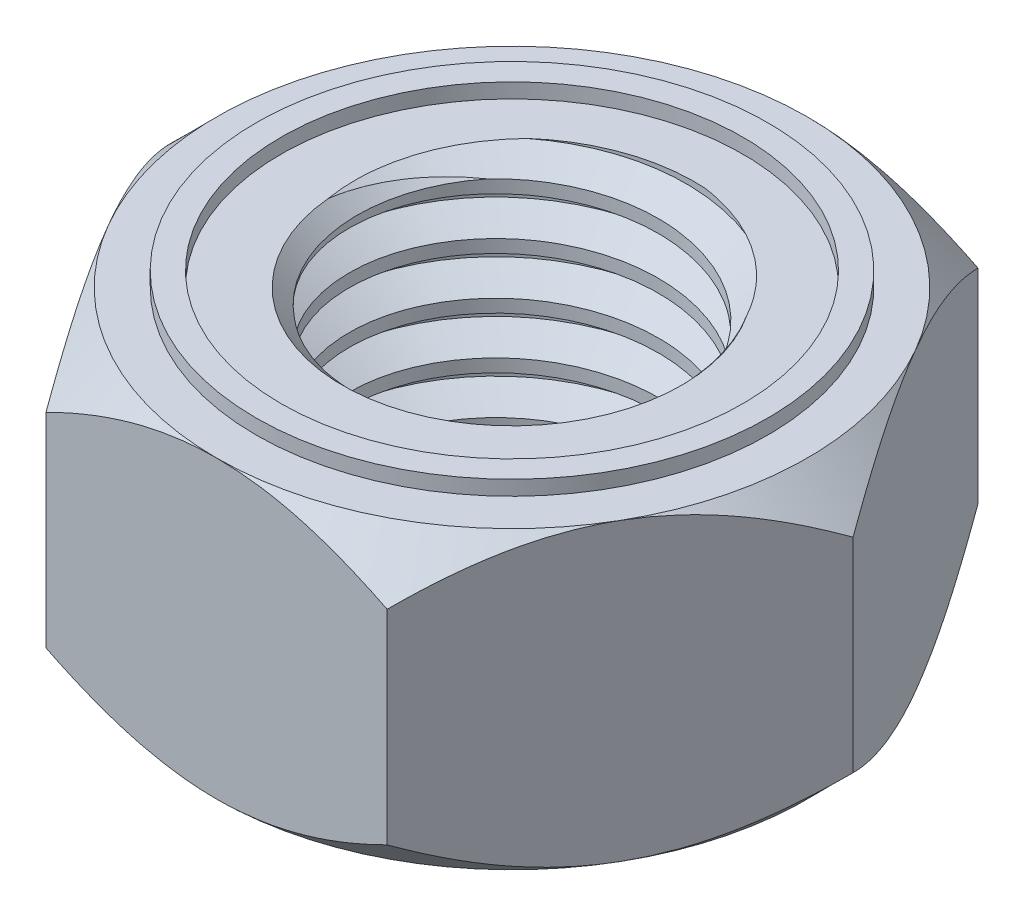
SolidWorks part; units mm, degrees
ref_plane "Front Plane" through (0, 0, 0) normal (0, 0, 1) x (1, 0, 0)
ref_plane "Top Plane" through (0, 0, 0) normal (0, 1, 0) x (1, 0, 0)
ref_plane "Right Plane" through (0, 0, 0) normal (1, 0, 0) x (0, 0, -1)
sketch "Sketch1" plane through (0, 0, 0) normal (0, 1, 0) x (1, 0, 0)
  line L1 (11.547, 0) -> (5.7735, 10)
  line L2 (5.7735, 10) -> (-5.7735, 10)
  line L3 (-5.7735, 10) -> (-11.547, 0)
  line L4 (-11.547, 0) -> (-5.7735, -10)
  line L5 (-5.7735, -10) -> (5.7735, -10)
  line L6 (5.7735, -10) -> (11.547, 0)
  circle A0 centre (0, 0) radius 10 construction
  dimension "D1" = 20
extrude "Boss-Extrude4" add sketch "Sketch1" along normal mid plane 10
sketch "Sketch4" plane through (0, 5, 0) normal (0, 1, 0) x (1, 0, 0)
  line L3 (-5.7735, -10) -> (5.7735, -10) construction
  circle A0 centre (0, 0) radius 10
extrude "Cut-Extrude2" cut sketch "Sketch4" against normal blind 10 draft 45 flip side to cut
mirror "Mirror2" about plane through (0, 0, 0) normal (0, 1, 0) of "Cut-Extrude2"
sketch "Sketch5" plane through (0, 5, 0) normal (0, 1, 0) x (1, 0, 0)
  circle A0 centre (0, 0) radius 5.24
  dimension "D1" = 10.48
extrude "Cut-Extrude3" cut sketch "Sketch5" against normal blind 10
chamfer "Chamfer1" distance 0.5 angle 45 2 edges at (0, -5, 5.24) (0, 5, 5.24)
thread "Thread1" pitch 1.75 start angle 0, offset 5, length 0, pitch 1.75, diameter 10.48
ref_plane "Plane1" through (-5.24, 9.5, 0) normal (0, 0, 1) x (-1, 0, 0)
sketch "Thread Profile1" plane through (-5.24, 9.5, 0) normal (0, 0, 1) x (-1, 0, 0)
  line L0 (0, 0) -> (0, 1.75) construction
  line L1 (0, 0) -> (0.9472, 0.5469)
  line L2 (0.9472, 0.5469) -> (0.9472, 0.7656)
  line L3 (0.9472, 0.7656) -> (0, 1.3125)
  line L4 (0.9472, 0.6562) -> (0, 0.6562) construction
  line L11 (0, 0) -> (0, 1.3125)
  point P2 (0, 0)
  dimension "Pitch" = 1.75
  dimension "Profile_Angle" = 60
  dimension "Profile_Land" = 0.2188
  dimension "Profile_Height" = 0.9472
sketch "Sketch8" plane through (0, 5, 0) normal (0, 1, 0) x (1, 0, 0)
  circle A0 centre (0, 0) radius 7.8159
  circle A1 centre (0, 0) radius 8.6594
extrude "Boss-Extrude6" add sketch "Sketch8" along normal blind 0.5
